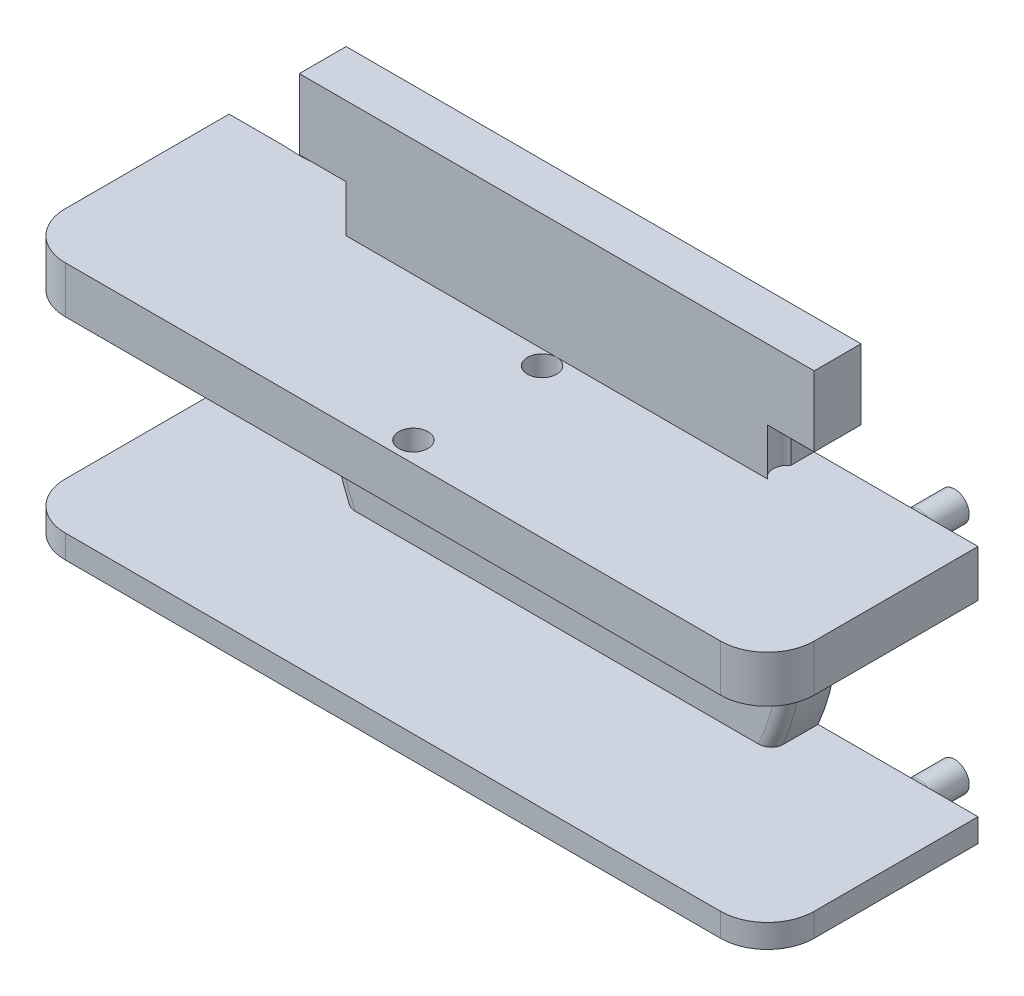
SolidWorks part; units mm, degrees
material "UNOBTANIUM"
ref_plane "Top Plane" through (0, 0, 0) normal (0, 0, 1) x (1, 0, 0)
ref_plane "Right Plane" through (0, 0, 0) normal (0, 1, 0) x (1, 0, 0)
ref_plane "Front Plane" through (0, 0, 0) normal (1, 0, 0) x (0, 0, -1)
ref_axis "x-axis" through (-17.6, 0, 0) along (1, 0, 0)
ref_axis "y-axis" through (0, -9.7375, 0) along (0, 1, 0)
ref_axis "z-axis" through (0, 0, 8.775) along (0, 0, -1)
sketch "Sketch1" plane through (0, 0, 0) normal (0, 0, 1) x (1, 0, 0)
  line L0 (-11, 6) -> (-11, 11)
  line L1 (-11, -6) -> (11, -6)
  line L2 (-11, -6) -> (-11, 6)
  line L3 (-11, 6) -> (11, 6) construction
  line L4 (11, -6) -> (11, 6)
  line L5 (-11, -6) -> (11, 6) construction
  line L6 (-11, 6) -> (11, -6) construction
  line L7 (-11, 11) -> (11, 11)
  line L8 (11, 11) -> (11, 6)
  circle A0 centre (0, 0) radius 9.25 construction
  point P0 (0, 0)
  dimension "D1" = 18.5
  dimension "D2" = 22
  dimension "D3" = 12
  dimension "D4" = 5
extrude "Boss-Extrude1" add sketch "Sketch1" along normal blind 2
sketch "Sketch2" plane through (0, 0, 2) normal (0, 0, -1) x (-1, 0, 0)
  circle A0 centre (0, 0) radius 1.575
  dimension "D1" = 3.15
extrude "Boss-Extrude2" add sketch "Sketch2" along normal blind 4 separate body
sketch "Sketch3" plane through (0, 0, 0) normal (0, 0, -1) x (-1, 0, 0)
  line L0 (11, -6) -> (-11, 6) construction
  circle A0 centre (0, 0) radius 1.8
  dimension "D1" = 3.6
extrude "Boss-Extrude3" add sketch "Sketch3" along normal blind 0.75
sketch "Sketch4" plane through (0, 0, 0) normal (0, 0, -1) x (-1, 0, 0)
  line L0 (11, -6) -> (-11, -6) construction
  line L1 (11, 11) -> (9, 11)
  line L2 (11, 11) -> (11, -6)
  line L3 (11, -6) -> (9, -6)
  line L4 (9, 11) -> (9, -6)
  line L5 (0, -6) -> (0, 11) construction
  line L7 (-9, 11) -> (-9, -6)
  line L8 (-11, -6) -> (-9, -6)
  line L9 (-11, 11) -> (-11, -6)
  line L10 (-11, 11) -> (-9, 11)
  line L11 (11, 11) -> (-11, 11) construction
  dimension "D1" = 2
extrude "Boss-Extrude4" add sketch "Sketch4" along normal blind 0.001
sketch "Sketch5" plane through (0, 0, 0) normal (0, 0, -1) x (-1, 0, 0)
  line L0 (-9, -6) -> (-9, 11) construction
  line L1 (9, 11) -> (-9, 11)
  line L2 (9, 11) -> (9, 9)
  line L3 (9, 9) -> (-9, 9)
  line L4 (-9, 11) -> (-9, 9)
  dimension "D1" = 2
extrude "Boss-Extrude5" add sketch "Sketch5" along normal up to surface (0.001 mm away) up to face at (-10, 2.5, -0.001)
sketch "Sketch6" plane through (11, 0, 0) normal (1, 0, 0) x (0, 0, -1)
  line L0 (-2, -6) -> (-2, 11) construction
  line L1 (0.001, -6) -> (-2, -6)
  line L2 (0.001, -6) -> (0.001, -4)
  line L3 (0.001, -4) -> (-2, -4)
  line L4 (-2, -6) -> (-2, -4)
  line L6 (0.001, 11) -> (0.001, -6) construction
  line L7 (-2, 6) -> (0.001, 6)
  line L8 (-2, 6) -> (-2, 4)
  line L9 (-2, 4) -> (0.001, 4)
  line L10 (0.001, 6) -> (0.001, 4)
  dimension "D1" = 2
extrude "Boss-Extrude6" add sketch "Sketch6" along normal blind 5
mirror "Mirror1" about plane through (0, 0, 0) normal (1, 0, 0) of "Boss-Extrude6"
sketch "Sketch7" plane through (0, 0, -0.001) normal (0, 0, -1) x (-1, 0, 0)
  line L0 (-9, -6) -> (-9, 9) construction
  line L1 (-9, 0) -> (-9, 9)
  line L2 (-9, 9) -> (0, 9)
  line L3 (-9, 0) -> (-9, -6)
  line L4 (-9, -6) -> (-6.7082, -6)
  line L5 (11, -6) -> (-11, -6) construction
  arc A0 (0, 9) -> (-6.7082, -6) centre (0, 0) ccw
  line M18 (-9, -6) -> (-9, 9)
  line M19 (-9, 9) -> (9, 9)
extrude "Boss-Extrude7" add sketch "Sketch7" against normal up to surface (0.001 mm away) contours A0 L4 M18 | A0 M19 M18 region at (8.3306, -4.5409, -0.001) region at (6.9897, 6.9897, -0.001) up to face at (1.8, 0, 0)
sketch "Sketch8" plane through (0, 0, -0.001) normal (0, 0, -1) x (-1, 0, 0)
  line L0 (-11, 4) -> (-9.1652, 4)
  line L1 (-11, 4) -> (-11, -4)
  line L2 (-11, -4) -> (-9.1652, -4)
  arc A1 (-9.1652, 4) -> (-9.1652, -4) centre (0, 0) ccw
  dimension "D1" = 10
extrude "Cut-Extrude1" cut sketch "Sketch8" against normal through all
sketch "Sketch9" plane through (0, 0, -0.001) normal (0, 0, -1) x (-1, 0, 0)
  line L0 (-16, -4) -> (-9.1652, -4) construction
  line L1 (-8.0623, 4) -> (-11, 4)
  line L2 (-8.0623, 4) -> (-8.0623, -4)
  line L3 (-8.0623, -4) -> (-11, -4)
  line L4 (-11, 4) -> (-11, -4)
  line L5 (-11, -6) -> (-11, 6) construction
  arc A0 (0, 9) -> (-6.7082, -6) centre (0, 0) ccw construction
  arc A1 (0, 9) -> (-6.7082, -6) centre (0, 0) ccw construction
extrude "Cut-Extrude2" cut sketch "Sketch9" against normal up to surface (0.001 mm away) up to face at (1.8, 0, 0)
mirror "Mirror2" about plane through (0, 0, 0) normal (1, 0, 0) of "Cut-Extrude2", "Boss-Extrude7", "Cut-Extrude1"
sketch "Sketch21" plane through (0, 0, -0.001) normal (0, 0, -1) x (-1, 0, 0)
  circle A0 centre (0, 0) radius 9.75
  circle A1 centre (0, 0) radius 9 construction
  circle A2 centre (0, 0) radius 1.8 construction
  circle A3 centre (0, 0) radius 1.8
  dimension "D1" = 0.75
extrude "Cut-Extrude11" cut sketch "Sketch21" against normal up to surface (0.001 mm away) up to face at (0, -0.7091, 0)
sketch "Sketch10" plane through (0, 0, 2) normal (0, 0, 1) x (1, 0, 0)
  line L0 (-16, -4) -> (-16, -6) construction
  line L1 (16, -6) -> (-16, -6)
  line L2 (16, -6) -> (16, -4)
  line L3 (16, -4) -> (-16, -4)
  line L4 (-16, -6) -> (-16, -4)
  line L5 (-16, -4) -> (-9.1652, -4) construction
  line L7 (-16, 6) -> (16, 6)
  line L8 (-16, 6) -> (-16, 4)
  line L9 (-16, 4) -> (16, 4)
  line L10 (16, 6) -> (16, 4)
extrude "Boss-Extrude8" add sketch "Sketch10" along normal blind 7
fillet "Fillet1" radius 0.5 2 edges at (10, 0, 2) (-10, 0, 2)
sketch "Sketch11" plane through (0, 0, -0.001) normal (0, 0, -1) x (-1, 0, 0)
  line L0 (-16, -5) -> (-13, -5) construction
  line L1 (-16, -6) -> (-16, -4) construction
  circle A0 centre (-13, -5) radius 0.625
  dimension "D1" = 1.25
  dimension "D2" = 3
extrude "Boss-Extrude9" add sketch "Sketch11" along normal blind 2
sketch "Sketch14" plane through (0, 0, -0.001) normal (0, 0, -1) x (-1, 0, 0)
  line L1 (11, 6) -> (9, 6)
  line L2 (11, 6) -> (11, 8)
  line L3 (11, 8) -> (9, 8)
  line L4 (9, 6) -> (9, 8)
  line L5 (-11, 6) -> (-9, 6)
  line L6 (-11, 6) -> (-11, 8)
  line L7 (-11, 8) -> (-9, 8)
  line L8 (-9, 6) -> (-9, 8)
  dimension "D1" = 18
  dimension "D2" = 2
extrude "Cut-Extrude5" cut sketch "Sketch14" against normal through all
sketch "Sketch12" plane through (0, 0, -0.001) normal (0, 0, -1) x (-1, 0, 0)
  line L0 (-16, -5) -> (-13, -5) construction
  line L1 (-16, -6) -> (-16, -4) construction
  line L3 (16, -5) -> (13, -5) construction
  line L4 (16, -6) -> (16, -4) construction
  circle A0 centre (13, -5) radius 0.675
  circle A1 centre (-13, -5) radius 0.625 construction
  circle A2 centre (-13, -5) radius 0.625 construction
  dimension "D1" = 1.35
  dimension "D2" = 1.25
extrude "Cut-Extrude3" cut sketch "Sketch12" against normal blind 2.5
sketch "Sketch16" plane through (0, 6, 0) normal (0, 1, 0) x (1, 0, 0)
  line L0 (-9, -2) -> (-9, 0.001) construction
  line L1 (-9, -1) -> (-9, -2)
  arc A1 (-9, -1) -> (-9, -2) centre (-9.375, -1.5) cw
  dimension "D1" = 0.25
  dimension "D2" = 1
extrude "Cut-Extrude6" cut sketch "Sketch16" along normal blind 2
mirror "Mirror3" about plane through (0, 0, 0) normal (0, 1, 0) of "Boss-Extrude9", "Cut-Extrude3"
mirror "Mirror4" about plane through (0, 0, 0) normal (1, 0, 0) of "Cut-Extrude6"
fillet "Fillet2" radius 0.5 2 edges at (12.375, 5, -0.001) (13.625, -5, -0.001)
fillet "Fillet3" radius 0.5 2 edges at (-13.675, 5, -0.001) (-13.675, -5, -0.001)
fillet "Fillet4" radius 2 4 edges at (16, -5, 9) (16, 5, 9) (-16, -5, 9) (-16, 5, 9)
sketch "Sketch17" plane through (0, -6, 0) normal (0, -1, 0) x (1, 0, 0)
  line L0 (-16, 7) -> (-16, -0.001) construction
  line L1 (-14, 9) -> (14, 9) construction
  line L2 (16, 7) -> (16, -0.001) construction
  line L3 (-16, 7) -> (-16, -0.001)
  line L4 (-14, 9) -> (14, 9)
  line L5 (16, 7) -> (16, -0.001)
  line L6 (14.5, 7) -> (14.5, -0.001)
  line L8 (-14, 7.5) -> (14, 7.5)
  line L9 (-14.5, 7) -> (-14.5, -0.001)
  line L10 (14.5, -0.001) -> (16, -0.001)
  line L11 (-14.5, -0.001) -> (-16, -0.001)
  arc A0 (-14, 9) -> (-16, 7) centre (-14, 7) ccw construction
  arc A1 (16, 7) -> (14, 9) centre (14, 7) ccw construction
  arc A2 (-14, 9) -> (-16, 7) centre (-14, 7) ccw
  arc A3 (16, 7) -> (14, 9) centre (14, 7) ccw
  arc A4 (14.5, 7) -> (14, 7.5) centre (14, 7) ccw
  arc A5 (-14, 7.5) -> (-14.5, 7) centre (-14, 7) ccw
  dimension "D1" = 1.5
extrude "Cut-Extrude7" cut sketch "Sketch17" against normal blind 1 and the other way through all
sketch "Sketch19" plane through (0, 6, 0) normal (0, 1, 0) x (1, 0, 0)
  line L0 (9, -2) -> (-9, -2) construction
  line L1 (0, -2.625) -> (0, -2) construction
  line L2 (9, -2) -> (-9, -2) construction
  circle A0 centre (0, -2.625) radius 0.625
  circle A1 centre (0, -8.125) radius 0.625
  point P4 (0, -2)
  dimension "D1" = 1.25
  dimension "D2" = 5.5
extrude "Cut-Extrude9" cut sketch "Sketch19" against normal up to surface (2 mm away) up to face at (0.0154, 4, 1.9997)
sketch "Sketch20" plane through (0, 0, -0.001) normal (0, 0, -1) x (-1, 0, 0)
  line L0 (-9, 8) -> (-11, 8) construction
  line L1 (-11, 11) -> (-9, 11)
  line L2 (-11, 11) -> (-11, 8)
  line L3 (-11, 8) -> (-9, 8)
  line L4 (-9, 11) -> (-9, 8)
  line L5 (11, 11) -> (-11, 11) construction
  line L6 (11, 8) -> (9, 8)
  line L7 (11, 8) -> (11, 11)
  line L8 (11, 11) -> (9, 11)
  line L9 (9, 8) -> (9, 11)
  dimension "D1" = 2
combine bodies "Combine2" operation type subtract main body 122 bodies to subtract 102
equation "\"D1@Sketch12\"=\"D2@Sketch12\"+.1"
